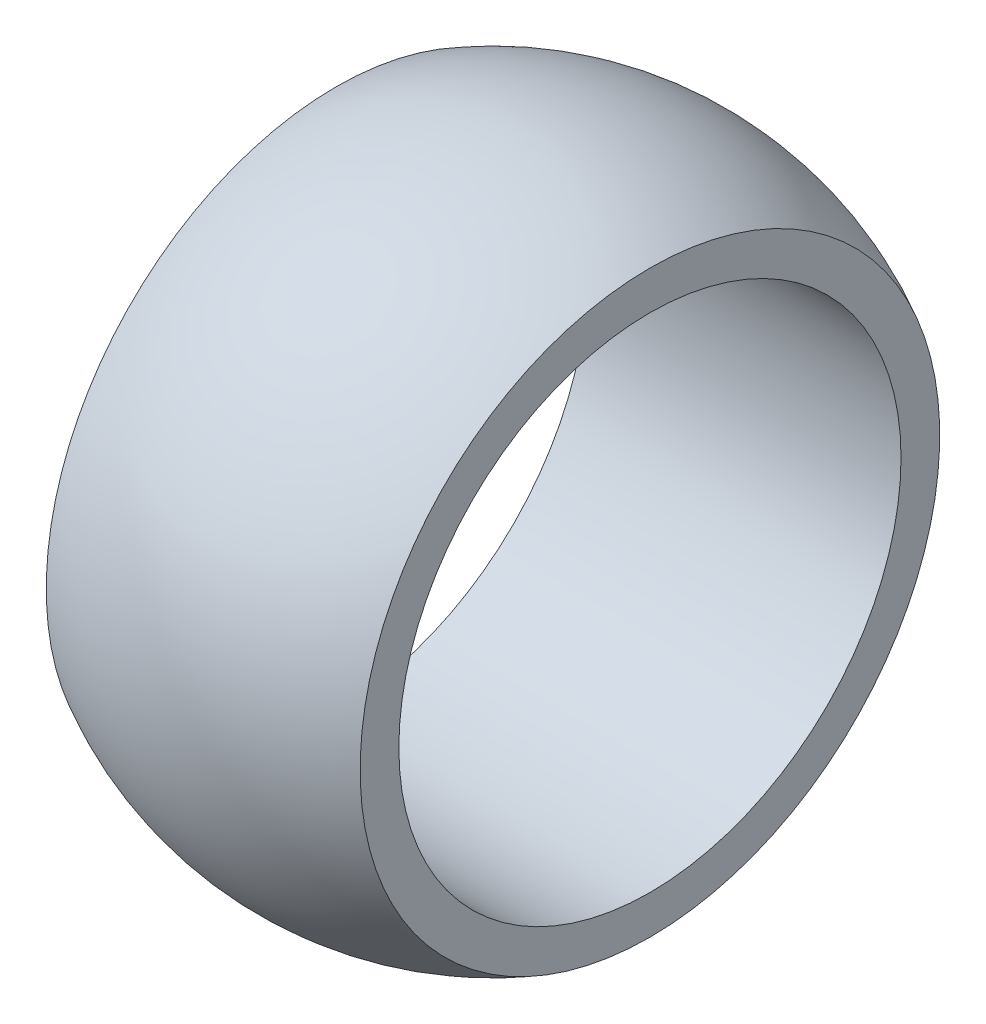
SolidWorks part; units mm, degrees
ref_plane "Face" through (0, 0, 0) normal (0, 0, 1) x (1, 0, 0)
ref_plane "Dessus" through (0, 0, 0) normal (0, 1, 0) x (1, 0, 0)
ref_plane "Droite" through (0, 0, 0) normal (1, 0, 0) x (0, 0, -1)
sketch "Esquisse1" plane through (0, 0, 0) normal (0, 0, 1) x (1, 0, 0)
  line L0 (2.5, 4.6165) -> (2.5, 4)
  line L1 (-2.5, 4.6165) -> (-2.5, 4)
  line L3 (-2.5, 4) -> (2.5, 4)
  line L6 (-124.153, 0) -> (93.8513, 0) construction
  arc A0 (2.5, 4.6165) -> (-2.5, 4.6165) centre (0, 0) ccw
  dimension "D1" = 10.5
  dimension "D2" = 4
  dimension "D3" = 2.5
  dimension "D4" = 5
revolve "Base-Révolution" add sketch "Esquisse1" angle 360 about L6
ref_axis "Axe1" through (2.5, 0, 0) along (-1, 0, 0)
